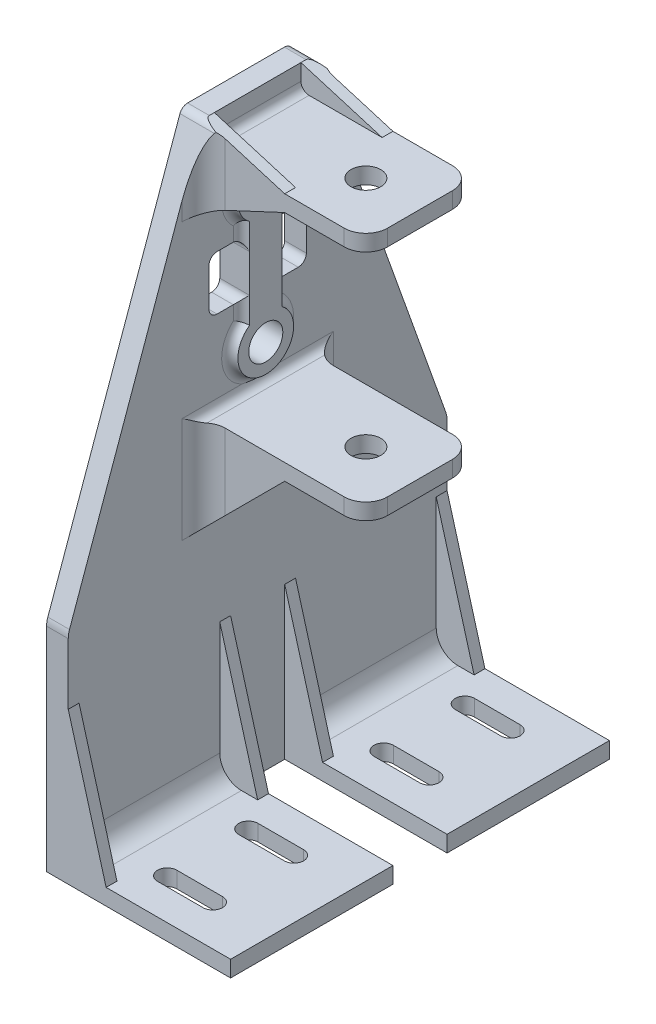
SolidWorks part; units mm, degrees
ref_plane "Alzado" through (0, 0, 0) normal (0, 0, 1) x (1, 0, 0)
ref_plane "Planta" through (0, 0, 0) normal (0, 1, 0) x (1, 0, 0)
ref_plane "Vista lateral" through (0, 0, 0) normal (1, 0, 0) x (0, 0, -1)
sketch "Croquis1" plane through (0, 0, 0) normal (1, 0, 0) x (0, 0, -1)
  line L0 (-10, 110) -> (-35, 40)
  line L1 (-35, 110) -> (35, 110) construction
  line L2 (-35, 110) -> (-35, 0) construction
  line L3 (-35, 0) -> (35, 0)
  line L4 (35, 110) -> (35, 0) construction
  line L5 (10, 110) -> (35, 40)
  line L6 (-10, 110) -> (10, 110)
  line L7 (-35, 40) -> (-35, 0)
  line L8 (35, 40) -> (35, 0)
  point P5 (0, 0)
  point P10 (0, 110)
  dimension "D1" = 110
  dimension "D2" = 70
  dimension "D3" = 70
  dimension "D4" = 20
extrude "Saliente-Extruir1" add sketch "Croquis1" along normal blind 4
sketch "Croquis2" plane through (4, 0, 0) normal (1, 0, 0) x (0, 0, -1)
  line L0 (0, 95) -> (0, 70) construction
  circle A0 centre (0, 70) radius 3.15
  circle A1 centre (0, 95) radius 3.15
  point P4 (0, 0)
  dimension "D2" = 6.3
  dimension "D1" = 25
  dimension "D3" = 70
extrude "Cortar-Extruir1" cut sketch "Croquis2" against normal blind 4
sketch "Croquis3" plane through (4, 0, 0) normal (1, 0, 0) x (0, 0, -1)
  line L0 (0, 95) -> (0, 70) construction
  line L1 (-3, 74.186) -> (3, 74.186) construction
  line L2 (-3, 74.186) -> (-3, 90.814)
  line L3 (-3, 90.814) -> (3, 90.814) construction
  line L4 (3, 74.186) -> (3, 90.814)
  line L5 (-3, 74.186) -> (3, 90.814) construction
  line L6 (-3, 90.814) -> (3, 74.186) construction
  circle A0 centre (0, 95) radius 5.15
  circle A1 centre (0, 70) radius 5.15
  circle A2 centre (0, 95) radius 3.15 construction
  point P3 (0, 0)
  point P8 (0, 82.5)
  point P13 (-3, 82.5)
  point P14 (0, 0)
  point P17 (0, 0)
  circle M5 centre (0, 95) radius 3.15
  circle M6 centre (0, 70) radius 3.15
  dimension "D1" = 2
  dimension "D2" = 6
extrude "Saliente-Extruir2" add sketch "Croquis3" along normal blind 1.5 contours A0 M5 | A1 M6 | A1 L4 A0 L2 region at (4, 82.5, 0) region at (4, 75.0043, 0) region at (4, 99.4515, 2.2864)
sketch "Croquis4" plane through (4, 0, 0) normal (1, 0, 0) x (0, 0, -1)
  line L0 (0, 95) -> (0, 70) construction
  line L1 (-9, 87.5) -> (9, 87.5)
  line L2 (-9, 87.5) -> (-9, 77.5)
  line L3 (-9, 77.5) -> (9, 77.5)
  line L4 (9, 87.5) -> (9, 77.5)
  line L5 (-9, 87.5) -> (9, 77.5) construction
  line L6 (-9, 77.5) -> (9, 87.5) construction
  line L7 (-3, 87.5) -> (-3, 77.5)
  line L8 (-3, 74.186) -> (-3, 90.814) construction
  line L9 (3, 87.5) -> (3, 77.5)
  line L10 (3, 74.186) -> (3, 90.814) construction
  point P0 (0, 82.5)
  line M10 (-3, 74.186) -> (-3, 90.814)
  line M12 (3, 90.814) -> (3, 74.186)
  dimension "D1" = 18
  dimension "D2" = 10
extrude "Cortar-Extruir2" cut sketch "Croquis4" against normal blind 4 contours L4 L1 L3 M12 | L2 L3 L1 M10 region at (4, 82.5, 6) region at (4, 82.5, -6)
sketch "Croquis5" plane through (4, 0, 0) normal (1, 0, 0) x (0, 0, -1)
  line L0 (3, 74.186) -> (3, 90.814) construction
  line L1 (-10, 62.5) -> (10, 62.5)
  line L2 (-10, 62.5) -> (-10, 59.5)
  line L3 (-10, 59.5) -> (10, 59.5)
  line L4 (10, 62.5) -> (10, 59.5)
  line L5 (-10, 62.5) -> (10, 59.5) construction
  line L6 (-10, 59.5) -> (10, 62.5) construction
  line L8 (-10, 105.5) -> (10, 105.5)
  line L9 (-10, 105.5) -> (-10, 102.5)
  line L10 (-10, 102.5) -> (10, 102.5)
  line L11 (10, 105.5) -> (10, 102.5)
  line L12 (-10, 105.5) -> (10, 102.5) construction
  line L13 (-10, 102.5) -> (10, 105.5) construction
  point P0 (0, 61)
  point P7 (3, 82.5)
  point P8 (0, 104)
  point P14 (0, 0)
  dimension "D1" = 20
  dimension "D2" = 3
  dimension "D3" = 20
  dimension "D4" = 40
extrude "Saliente-Extruir3" add sketch "Croquis5" along normal blind 30
sketch "Croquis6" plane through (0, 62.5, 0) normal (0, 1, 0) x (1, 0, 0)
  line L0 (4, 10) -> (4, -10) construction
  circle A0 centre (24, 0) radius 2.75
  point P4 (0, 0)
  dimension "D1" = 5.5
  dimension "D2" = 20
extrude "Cortar-Extruir3" cut sketch "Croquis6" against normal through all both and the other way through all
sketch "Croquis7" plane through (4, 0, 0) normal (1, 0, 0) x (0, 0, -1)
  line L1 (-35, 0) -> (-5, 0)
  line L2 (-35, 0) -> (-35, 3)
  line L3 (-35, 3) -> (-5, 3)
  line L4 (-5, 0) -> (-5, 3)
  dimension "D1" = 3
  dimension "D2" = 30
extrude "Saliente-Extruir4" add sketch "Croquis7" along normal blind 30
hole_wizard "Diámetro de taladro 9/64 (0.14063)1" positions "Croquis8" profile "Croquis9" size "9/64" standard "Ansi Inch" slot yes end condition up to next
sketch "Croquis8" plane through (0, 3, 0) normal (0, 1, 0) x (1, 0, 0)
  line L0 (13, -27.5) -> (25, -27.5) construction
  line L2 (34, -5) -> (34, -35) construction
  line L3 (19, -27.5) -> (19, -12.5) construction
  point P0 (19, -27.5)
  point P4 (19, -12.5)
  point P22 (19, -20)
  point P23 (34, -20)
  dimension "D1" = 12
  dimension "D2" = 15
  dimension "D3" = 15
sketch "Croquis9" plane through (19, 3, 27.5) normal (1, 0, 0) x (0, 0, 1)
  line L0 (0, 0) -> (0, 3.001)
  line L1 (0, 3.001) -> (1.786, 3.001)
  line L2 (1.786, 3.001) -> (1.786, 0)
  line L5 (1.786, 0) -> (0, 0)
  line L11 (0, -6.35) -> (0, 107.95) construction
  dimension "Diámetro de taladro hasta el siguiente" = 3.572
  dimension "Profundidad de taladro hasta el siguiente" = 3.001
sketch "Croquis10" plane through (0, 0, 10) normal (0, 0, 1) x (1, 0, 0)
  line L0 (19, 102.5) -> (4, 95.482)
  line L1 (34, 102.5) -> (4, 102.5) construction
  line L2 (4, 90.814) -> (4, 100.15) construction
rib "Nervio1" sketch "Croquis10" sketch "Croquis10" thickness 2 extrusion direction parallel to sketch draft on no parameters "D1"=2
sketch "Croquis12" plane through (0, 0, 10) normal (0, 0, 1) x (1, 0, 0)
  line L0 (19, 105.5) -> (4, 110)
  line L1 (34, 105.5) -> (4, 105.5) construction
rib "Nervio15" sketch "Croquis12" sketch "Croquis12" thickness 2 extrusion direction parallel to sketch draft on no parameters "D1"=2
sketch "Croquis13" plane through (0, 0, 10) normal (0, 0, 1) x (1, 0, 0)
  line L0 (19, 59.5) -> (4, 44.5)
  line L1 (34, 59.5) -> (4, 59.5) construction
  line L2 (4, 40) -> (4, 3) construction
  dimension "D1" = 15
rib "Nervio16" sketch "Croquis13" sketch "Croquis13" thickness 2 extrusion direction parallel to sketch draft on no parameters "D1"=2
sketch "Croquis14" plane through (0, 0, 35) normal (0, 0, 1) x (1, 0, 0)
  line L0 (4, 28) -> (11, 3)
  line L1 (4, 40) -> (4, 3) construction
  line L2 (34, 3) -> (4, 3) construction
  dimension "D1" = 7
  dimension "D2" = 25
rib "Nervio17" sketch "Croquis14" sketch "Croquis14" thickness 2 extrusion direction parallel to sketch draft on no parameters "D1"=2
sketch "Croquis15" plane through (0, 0, 5) normal (0, 0, -1) x (-1, 0, 0)
  line L0 (-11, 3) -> (-4, 28)
  line L1 (-34, 3) -> (-4, 3) construction
  line L2 (-11, 3) -> (-4, 3) construction
  line L3 (-4, 0) -> (-4, 40) construction
  line L4 (-4, 28) -> (-11, 3) construction
  point P10 (-17.3955, 3)
rib "Nervio18" sketch "Croquis15" sketch "Croquis15" thickness 2 extrusion direction parallel to sketch draft on no parameters "D1"=2
mirror "Simetría1" about plane through (0, 0, 0) normal (0, 0, 1) of "Diámetro de taladro 9/64 (0.14063)1", "Saliente-Extruir4", "Nervio18", "Nervio17", "Nervio16", "Nervio15", "Nervio1"
fillet "Redondeo2" radius 4 12 edges at (34, 61, -10) (34, 61, 10) (34, 104, -10) (34, 104, 10) (4, 3, 20) (4, 3, -20) (4, 102.741, 10) (4, 102.741, -10) (4, 53.5, -10) (4, 53.5, 10) (2, 40, 35) (2, 40, -35)
fillet "Redondeo3" radius 1.5 20 edges at (4, 59.5, 0) (2, 77.5, -9) (2, 87.5, -9) (2, 77.5, 9) (2, 87.5, 9) (4, 62.5, 0) (4, 102.5, 0) (2, 77.5, 3) (4, 75.843, 3) (4, 64.85, 0) (4, 75.843, -3) (2, 77.5, -3) (2, 87.5, -3) (4, 89.157, -3) (2, 87.5, 3) (4, 89.157, 3) (4, 100.15, 0) (4, 105.5, 0) (2, 110, -10) (2, 110, 10)
